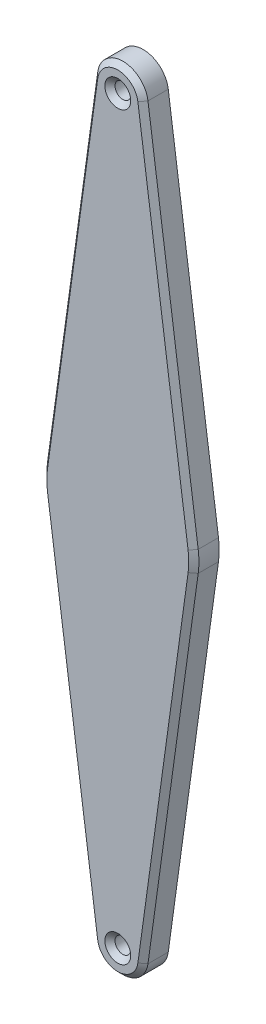
SolidWorks part; units mm, degrees
ref_plane "Front Plane" through (0, 0, 0) normal (0, 0, 1) x (1, 0, 0)
ref_plane "Top Plane" through (0, 0, 0) normal (0, 1, 0) x (1, 0, 0)
ref_plane "Right Plane" through (0, 0, 0) normal (1, 0, 0) x (0, 0, -1)
sketch "Sketch1" plane through (0, 0, 0) normal (0, 0, 1) x (1, 0, 0)
  line L1 (191, 68) -> (85, 68)
  line L2 (85, 68) -> (85, 141) construction
  line L3 (89.9529, 141.6849) -> (99.8586, 70.0548)
  line L8 (0, 136) -> (0, 0)
  line L9 (0, 0) -> (191, 0)
  line L10 (191, 0) -> (191, 136)
  line L11 (191, 136) -> (0, 136)
  line L12 (80.0471, 141.6849) -> (70.1414, 70.0548)
  line L13 (89.9529, -5.6849) -> (99.8586, 65.9452)
  line L14 (80.0471, -5.6849) -> (70.1414, 65.9452)
  circle A0 centre (85, 68) radius 15
  circle A1 centre (85, 141) radius 5
  circle A2 centre (85, -5) radius 5
  dimension "D2" = 30
  dimension "D4" = 10
  dimension "D3" = 5
extrude "Boss-Extrude1" add sketch "Sketch1" along normal blind 5 contours L2 A0 L3 L11 | A0 L2 L11 L12 | A1 | A1 L11 L3 | A1 L12 L11 | L1 L2 A0 | L2 L1 A0 | A0 L14 L9 L13 | L14 A2 L9 | L9 A2 L13 | A2 region at (82.8779, 65.8779, 0) region at (91.3662, 74.3662, 0) region at (90.3088, 104.3689, 0) region at (85, 31.6311, 0) region at (89.2502, -1.2971, 0) region at (89.2502, 137.2971, 0) region at (79.6912, 104.3689, 0) region at (80.7498, -1.2971, 0) region at (85, -5, 0) region at (89.8471, 141.3336, 0) region at (80.7498, 137.2971, 0)
chamfer "Chamfer1" distance 1 angle 45 8 edges at (75.0943, 30.1301, 5) (70, 68, 5) (75.0943, 105.8699, 5) (85, 146, 5) (94.9057, 105.8699, 5) (100, 68, 5) (94.9057, 30.1301, 5) (85, -10, 5)
sketch "Sketch6" plane through (0, 0, 5) normal (0, 0, 1) x (1, 0, 0)
  circle A0 centre (85, 141) radius 1.55
  dimension "D1" = 3.1
extrude "Cut-Extrude2" cut sketch "Sketch6" against normal up to next contours A0 region at (85, 141, 5)
chamfer "Chamfer3" distance 1 angle 45 1 edges at (86.55, 141, 5)
sketch "Sketch7" plane through (0, 0, 5) normal (0, 0, 1) x (1, 0, 0)
  line L1 (190.9967, 68.8326) -> (85, 68) construction
  line L2 (190.9967, 68.8326) -> (85, 68) construction
ref_axis "Axis2" through (85, 68, 5) along (0, 0, -1)
sketch "Sketch8" plane through (0, 0, 0) normal (0, 0, -1) x (-1, 0, 0)
  line L0 (-100, 68) -> (-70, 68) construction
  arc A0 (-99.8586, 70.0548) -> (-99.8586, 65.9452) centre (-85, 68) ccw construction
  arc A1 (-70.1414, 65.9452) -> (-70.1414, 70.0548) centre (-85, 68) ccw construction
ref_axis "Axis3" through (100, 68, 0) along (-1, 0, 0)
ref_plane "Plane3" through (0, 68, 0) normal (0, -1, 0) x (-1, 0, 0)
mirror "Mirror2" about plane through (0, 68, 0) normal (0, -1, 0) of "Cut-Extrude2", "Chamfer3"
